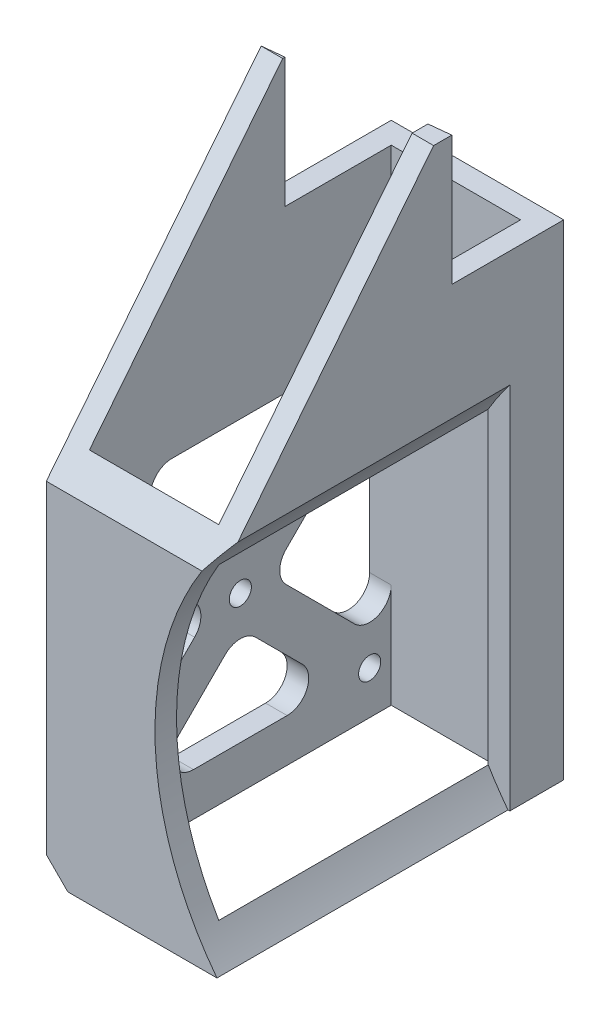
SolidWorks part; units mm, degrees
material "6061-T6 (SS)"
ref_plane "Front Plane" through (0, 0, 0) normal (0, 0, 1) x (1, 0, 0)
ref_plane "Top Plane" through (0, 0, 0) normal (0, 1, 0) x (1, 0, 0)
ref_plane "Right Plane" through (0, 0, 0) normal (1, 0, 0) x (0, 0, -1)
sketch "Sketch1" plane through (0, 0, 0) normal (0, 1, 0) x (1, 0, 0)
  line L1 (-12.7, -25.4) -> (12.7, -25.4)
  line L2 (-12.7, -25.4) -> (-12.7, 25.4)
  line L3 (-12.7, 25.4) -> (12.7, 25.4)
  line L4 (12.7, -25.4) -> (12.7, 25.4)
  line L5 (-12.7, -25.4) -> (12.7, 25.4) construction
  line L6 (-12.7, 25.4) -> (12.7, -25.4) construction
  line L7 (-9.525, -22.225) -> (9.525, -22.225)
  line L8 (-9.525, -22.225) -> (-9.525, 22.225)
  line L9 (-9.525, 22.225) -> (9.525, 22.225)
  line L10 (9.525, -22.225) -> (9.525, 22.225)
  line L11 (-9.525, -22.225) -> (9.525, 22.225) construction
  line L12 (-9.525, 22.225) -> (9.525, -22.225) construction
  point P0 (0, 0)
  point P6 (0, 0)
  dimension "D1" = 25.4
  dimension "D2" = 19.05
  dimension "D3" = 50.8
  dimension "D4" = 44.45
extrude "Boss-Extrude1" add sketch "Sketch1" along normal blind 90.4875
sketch "Sketch2" plane through (0, 90.4875, 0) normal (0, 1, 0) x (1, 0, 0)
  line L0 (-12.7, 25.4) -> (-36.83, 22.86) construction
  line L1 (-36.83, 22.86) -> (-12.7, 22.86) construction
  line L2 (-12.7, 25.4) -> (-12.7, -25.4) construction
  line L3 (-12.7, 22.86) -> (-12.7, 25.4) construction
  line L4 (-12.7, 6.2448) -> (12.7, 8.9184)
  line L5 (-12.7, 6.2448) -> (-12.7, 25.4)
  line L6 (12.7, 25.4) -> (12.7, 8.9184)
  line L7 (12.7, -25.4) -> (12.7, 25.4) construction
  line L8 (-12.7, 25.4) -> (12.7, 25.4)
  dimension "D1" = 2.54
  dimension "D2" = 24.13
  dimension "D3" = 19.05
extrude "Cut-Extrude1" cut sketch "Sketch2" against normal blind 19.05
sketch "Sketch3" plane through (-12.7, 0, 0) normal (-1, 0, 0) x (0, 0, 1)
  line L0 (-6.2448, 90.4875) -> (25.4, 50.8)
  line L1 (25.4, 90.4875) -> (25.4, 0) construction
  line L3 (-25.4, 0) -> (25.4, 0) construction
  line L5 (-25.4, 0) -> (-25.4, 50.8) construction
  line L6 (-25.4, 50.8) -> (25.4, 50.8) construction
  line L7 (25.4, 50.8) -> (-25.4, 0) construction
  line L8 (-25.4, 50.8) -> (25.4, 0) construction
  line L9 (-16.8049, 37.7148) -> (-6.7352, 27.6451)
  line L10 (-6.7352, 23.1549) -> (-16.8049, 13.0852)
  line L11 (-22.225, 15.3303) -> (-22.225, 35.4697)
  line L12 (-12.3148, 42.2049) -> (-2.2451, 32.1352)
  line L13 (2.2451, 32.1352) -> (12.3148, 42.2049)
  line L14 (10.0697, 47.625) -> (-10.0697, 47.625)
  line L15 (0, 25.4) -> (25.4, 25.4) construction
  line L16 (0, 25.4) -> (0, -7.1438) construction
  line L17 (-6.8947, 6.35) -> (6.8947, 6.35)
  line L18 (2.2451, 18.6648) -> (9.1398, 11.7701)
  line L19 (-9.1398, 11.7701) -> (-2.2451, 18.6648)
  line L20 (22.225, 15.3303) -> (22.225, 35.4697)
  line L21 (6.7352, 23.1549) -> (16.8049, 13.0852)
  line L22 (16.8049, 37.7148) -> (6.7352, 27.6451)
  arc A0 (-22.225, 15.3303) -> (-16.8049, 13.0852) centre (-19.05, 15.3303) ccw
  arc A1 (-9.1398, 11.7701) -> (-6.8947, 6.35) centre (-6.8947, 9.525) ccw
  arc A2 (9.1398, 11.7701) -> (6.8947, 6.35) centre (6.8947, 9.525) cw
  arc A3 (22.225, 15.3303) -> (16.8049, 13.0852) centre (19.05, 15.3303) cw
  arc A4 (22.225, 35.4697) -> (16.8049, 37.7148) centre (19.05, 35.4697) ccw
  arc A5 (12.3148, 42.2049) -> (10.0697, 47.625) centre (10.0697, 44.45) ccw
  arc A6 (-12.3148, 42.2049) -> (-10.0697, 47.625) centre (-10.0697, 44.45) cw
  arc A7 (-22.225, 35.4697) -> (-16.8049, 37.7148) centre (-19.05, 35.4697) cw
  arc A8 (-2.2451, 18.6648) -> (2.2451, 18.6648) centre (0, 16.4197) cw
  arc A9 (6.7352, 23.1549) -> (6.7352, 27.6451) centre (8.9803, 25.4) cw
  arc A10 (2.2451, 32.1352) -> (-2.2451, 32.1352) centre (0, 34.3803) cw
  arc A11 (-6.7352, 23.1549) -> (-6.7352, 27.6451) centre (-8.9803, 25.4) ccw
  point P11 (19.05, 6.35)
  point P13 (-19.05, 6.35)
  point P14 (0, 25.4)
  point P15 (-19.05, 44.45)
  point P16 (19.05, 44.45)
  point P36 (-22.225, 7.6651)
  point P39 (-17.7349, 3.175)
  point P42 (17.7349, 3.175)
  point P45 (22.225, 7.6651)
  point P48 (22.225, 43.1349)
  point P51 (17.7349, 47.625)
  point P54 (-17.7349, 47.625)
  point P57 (-22.225, 43.1349)
  point P60 (0, 20.9099)
  point P63 (4.4901, 25.4)
  point P66 (0, 29.8901)
  point P69 (-4.4901, 25.4)
  line M1 (25.4, 90.4875) -> (-6.2448, 90.4875)
  line M6 (25.4, 0) -> (25.4, 90.4875)
  dimension "D11" = 3.175
  dimension "D13" = 3.175
  dimension "D1" = 39.6875
  dimension "D4" = 6.35
  dimension "D5" = 6.35
  dimension "D6" = 3.175
  dimension "D7" = 3.175
  dimension "D8" = 3.175
  dimension "D9" = 6.35
  dimension "D10" = 3.175
  dimension "D12" = 6.35
extrude "Cut-Extrude2" cut sketch "Sketch3" against normal blind 3.175 contours A10 L13 A5 L14 A6 L12 | L10 A11 L9 A7 L11 A0 | A8 L19 A1 L17 A2 L18 | A9 L21 A3 L20 A4 L22 region at (-12.7, 25.4, -16.0046) region at (-12.7, 41.4046, 0) region at (-12.7, 11.5655, 0) region at (-12.7, 25.4, 16.0046)
extrude "Cut-Extrude3" cut sketch "Sketch3<3>" against normal through all contours L0 M1 M6 region at (-12.7, 77.2583, 14.8517)
sketch "Sketch3<3>" plane through (-12.7, 0, 0) normal (-1, 0, 0) x (0, 0, 1) same geometry as "Sketch3"
hole_wizard "#30 (0.1285) Diameter Hole1" positions "Sketch5" profile "Sketch6" hole size "#30" standard "ANSI Inch"
sketch "Sketch5" plane through (-12.7, 0, 0) normal (-1, 0, 0) x (0, 0, 1)
  point P0 (-19.05, 44.45)
  point P3 (0, 25.4)
  point P6 (19.05, 44.45)
  point P9 (19.05, 6.35)
  point P12 (-19.05, 6.35)
sketch "Sketch6" plane through (-12.7, 44.45, -19.05) normal (0, 1, 0) x (0, 0, 1)
  line L0 (0, 0) -> (0, 4.1556)
  line L1 (0, 4.1556) -> (1.6319, 3.175)
  line L2 (1.6319, 3.175) -> (1.6319, 0)
  line L5 (1.6319, 0) -> (0, 0)
  line L10 (0, 4.1556) -> (-1.6319, 3.175) construction
  line L11 (0, -6.35) -> (0, 107.95) construction
  dimension "Hole Dia." = 3.2639
  dimension "Hole Depth" = 3.175
  dimension "Drill Angle" = 118
sketch "Sketch12" plane through (0, 0, 25.4) normal (0, 0, 1) x (1, 0, 0)
  line L0 (0, 0) -> (0, 50.8) construction
  line L1 (-12.7, 0) -> (12.7, 0) construction
  line L2 (12.7, 50.8) -> (-12.7, 50.8) construction
  line L3 (-12.7, 50.8) -> (12.7, 50.8) construction
  line L4 (-12.7, 50.8) -> (-12.7, 0) construction
  line L5 (12.7, 50.8) -> (12.7, 0) construction
  point P12 (0, 34.925)
  point P13 (0, 15.875)
  dimension "D1" = 50.8
  dimension "D2" = 15.875
  dimension "D3" = 15.875
sketch "Sketch15" plane through (0, 0, 25.4) normal (0, 0, 1) x (1, 0, 0)
  line L1 (-12.7, 0) -> (12.7, 0) construction
  circle A0 centre (47.752, 26.9875) radius 44.45
  point P5 (-12.7, 0)
  dimension "D1" = 88.9
  dimension "D2" = 60.452
  dimension "D3" = 26.9875
extrude "Cut-Extrude5" cut sketch "Sketch15" against normal blind 42.8625
chamfer "Chamfer1" distance 3.175 angle 45 1 edges at (-12.7, 0, 0)
